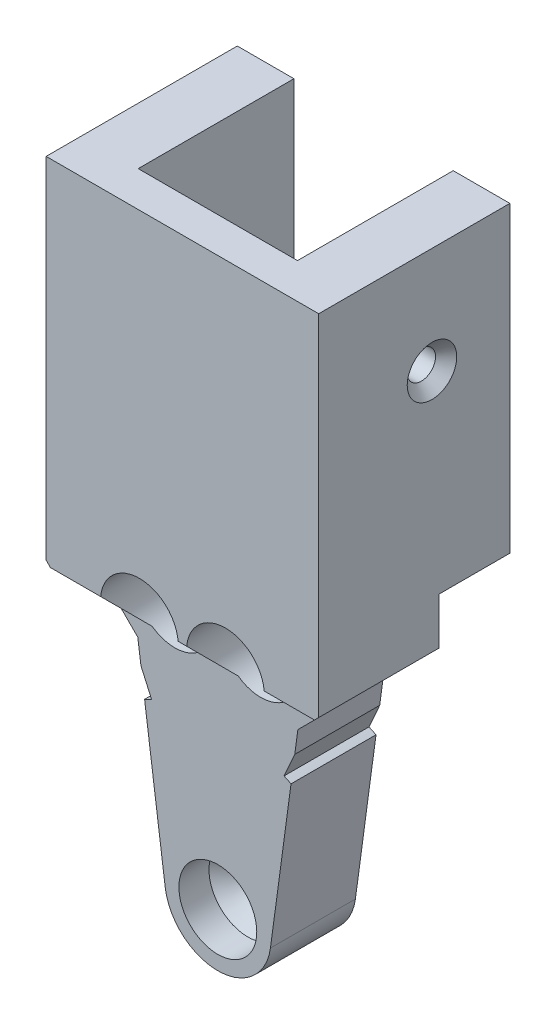
SolidWorks part; units mm, degrees
ref_plane "Top Plane" through (0, 0, 0) normal (0, 0, 1) x (1, 0, 0)
ref_plane "Right Plane" through (0, 0, 0) normal (0, 1, 0) x (1, 0, 0)
ref_plane "Front Plane" through (0, 0, 0) normal (1, 0, 0) x (0, 0, -1)
sketch "Sketch1" plane through (0, 0, 0) normal (0, 0, 1) x (1, 0, 0)
  line L0 (-15, 55) -> (0, 55)
  line L1 (0, 55) -> (0, 0) construction
  line L2 (7.4325, -1.0043) -> (15, 55) construction
  line L3 (-15, 55) -> (-10.8659, 24.4052)
  line L4 (-9.3549, 21.0115) -> (-10.8659, 24.4052)
  line L5 (-10.344, 20.5427) -> (-7.4325, -1.0043)
  line L6 (-10.8659, 24.4052) -> (-10.344, 20.5427) construction
  line L7 (-9.3549, 21.0115) -> (0, 0) construction
  line L8 (0, -7.5) -> (0, 55)
  line L9 (0, 55) -> (15, 55) construction
  line L10 (0, 0) -> (-6.0777, 34.4683) construction
  arc A0 (0, 2.75) -> (0, -2.75) centre (0, 0) ccw
  circle A1 centre (0, 0) radius 7.5 construction
  arc A2 (0, -7.5) -> (-7.4325, -1.0043) centre (0, 0) cw
  arc A3 (-9.3549, 21.0115) -> (10.344, 20.5427) centre (0, 0) cw construction
  arc A4 (-11.1837, 26.7568) -> (11.1837, 26.7568) centre (0, 0) cw construction
  arc A5 (-10.344, 20.5427) -> (-9.3549, 21.0115) centre (0, 0) cw
  circle A6 centre (-6.0777, 34.4683) radius 2.75
  arc A7 (7.4325, -1.0043) -> (0, -7.5) centre (0, 0) cw construction
  arc A8 (0, -2.75) -> (0, 2.75) centre (0, 0) ccw construction
  dimension "D1" = 5.5
  dimension "D2" = 15
  dimension "D5" = 23
  dimension "D6" = 6
  dimension "D8" = 5.5
  dimension "D3" = 30
  dimension "D4" = 55
  dimension "D7" = 24
  dimension "D9" = 35
  dimension "D10" = 10
extrude "Boss-Extrude1" add sketch "Sketch1" along normal blind 12 contours A5 L5 A2 L8 A0 L0 L3 L4 A6
sketch "Sketch3" plane through (0, 55, 0) normal (0, 1, 0) x (1, 0, 0)
  line L0 (0, -17) -> (-19.25, -17)
  line L1 (-19.25, -17) -> (-19.25, 10)
  line L2 (-19.25, 10) -> (-11.25, 10)
  line L3 (-11.25, 10) -> (-11.25, -12)
  line L4 (-11.25, -12) -> (0, -12)
  line L5 (0, -12) -> (0, 0) construction
  line L6 (0, -12) -> (0, -17)
  line L7 (-15, -12) -> (0, -12) construction
  point P4 (0, -13.8584)
  point P11 (0, -12)
  dimension "D1" = 11.25
  dimension "D2" = 22
  dimension "D3" = 5
  dimension "D4" = 8
extrude "Boss-Extrude2" add sketch "Sketch3" along normal blind 30 and the other way blind 10
chamfer "Chamfer1" distance 15 angle 45 2 edges at (-13.6488, 45, 6) (-6.8244, 45, 12)
sketch "Sketch4" plane through (-19.25, 0, 0) normal (-1, 0, 0) x (0, 0, 1)
  line L0 (1, 70) -> (1, 85) construction
  line L1 (-10, 85) -> (17, 85) construction
  line L3 (12, 85) -> (-10, 85) construction
  circle A0 centre (1, 70) radius 2
  point P6 (0, 0)
  point P8 (0, 0)
  dimension "D1" = 4
  dimension "D2" = 15
extrude "Cut-Extrude1" cut sketch "Sketch4" against normal blind 30
chamfer "Chamfer2" distance 1.5 angle 45 1 edges at (-19.25, 70, 3)
sketch "Sketch5" plane through (0, 0, 12) normal (0, 0, 1) x (1, 0, 0)
  circle A0 centre (0, 0) radius 5.5
  circle A1 centre (-6.0777, 34.4683) radius 5.5
  circle A2 centre (-6.0777, 34.4683) radius 2.75 construction
  dimension "D1" = 11
extrude "Cut-Extrude2" cut sketch "Sketch5" against normal offset from surface 18 and the other way blind 30
chamfer "Chamfer3" distance 3 angle 45 2 edges at (-2.75, 0, 8) (-8.8277, 34.4683, 8)
sketch "Sketch6" plane through (0, 0, 0) normal (0, 0, -1) x (-1, 0, 0)
  line L0 (19.25, 45) -> (19.25, 35.6012) construction
  line L1 (0, 2.75) -> (0, 55) construction
  line L2 (19.25, 42.2019) -> (19.25, 55)
  line L3 (19.25, 55) -> (0, 55)
  line L4 (0, 55) -> (0, 46.3849)
  arc A0 (19.25, 42.2019) -> (0, 46.3849) centre (0, 0) ccw
  arc A1 (0, -7.5) -> (7.4325, -1.0043) centre (0, 0) ccw construction
extrude "Boss-Extrude3" add sketch "Sketch6" along normal up to surface (10 mm away) up to face at (-15.25, 65, -10)
mirror "Mirror1" about plane through (0, 0, 12) normal (-1, 0, 0) of bodies 106 107
